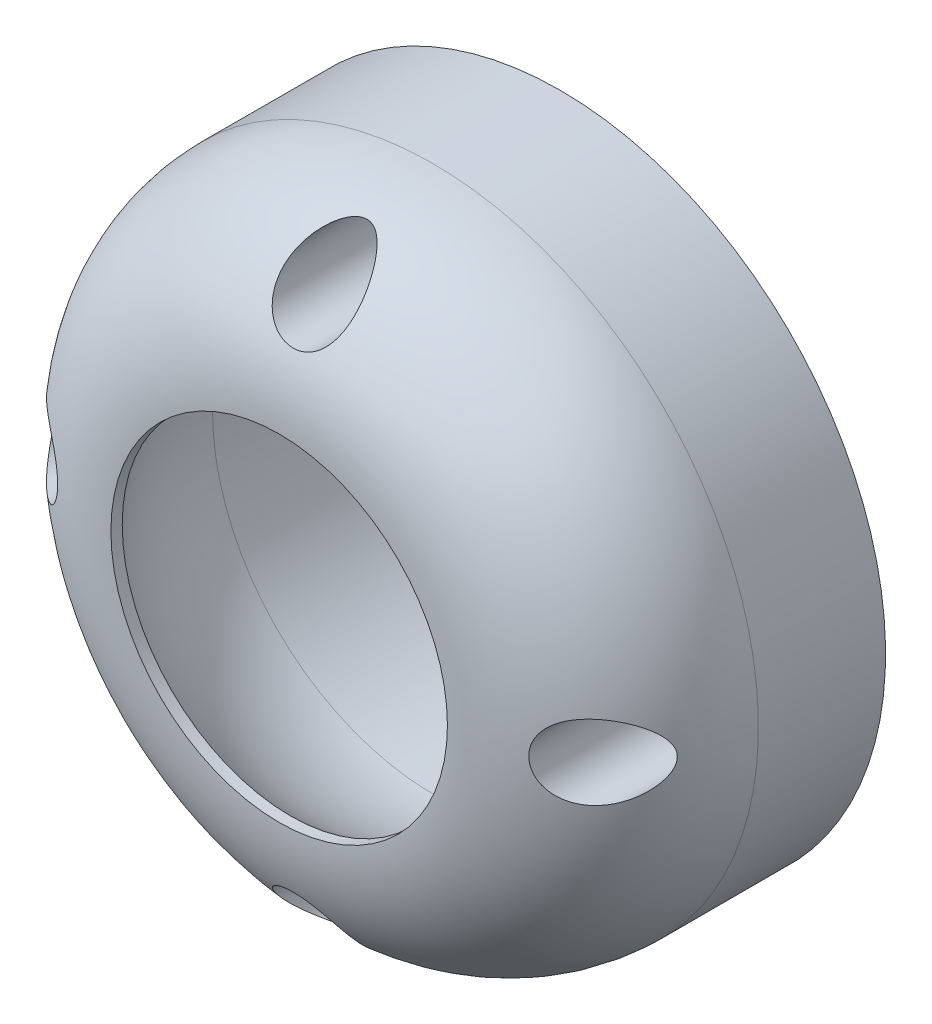
SolidWorks part; units mm, degrees
ref_plane "正面" through (0, 0, 0) normal (0, 0, 1) x (1, 0, 0)
ref_plane "平面" through (0, 0, 0) normal (0, 1, 0) x (1, 0, 0)
ref_plane "右側面" through (0, 0, 0) normal (1, 0, 0) x (0, 0, -1)
sketch "ｽｹｯﾁ1" plane through (0, 0, 0) normal (0, 0, 1) x (1, 0, 0)
  line L0 (-15.25, 0) -> (-14.75, 0)
  line L1 (14.75, 0) -> (15.25, 0)
  line L2 (14.75, 0) -> (-14.75, 0) construction
  arc A0 (14.75, 0) -> (-14.75, 0) centre (0, 0) cw
  arc A1 (-15.25, 0) -> (15.25, 0) centre (0, 0) ccw
  dimension "D2" = 14.75
  dimension "D1" = 15.25
revolve "回転1" add sketch "ｽｹｯﾁ1" angle 180 about L2
sketch "ｽｹｯﾁ2" plane through (0, 0, 0) normal (0, 0, -1) x (-1, 0, 0)
  circle A0 centre (0, 0) radius 11.25
  dimension "D1" = 22.5
extrude "ｶｯﾄ - 押し出し1" cut sketch "ｽｹｯﾁ2" against normal through all
sketch "ｽｹｯﾁ4" plane through (0, 0, 0) normal (1, 0, 0) x (0, 0, -1)
  line L0 (0, 15.25) -> (0, 21.75)
  line L1 (0, 0) -> (0, 15.25) construction
  line L2 (0, 0) -> (-17.7206, 0) construction
  arc A0 (-10.2956, 11.25) -> (0, 21.75) centre (0, 11.4524) cw
  arc A1 (0, 15.25) -> (-10.2956, 11.25) centre (0, 0) ccw
  arc A2 (0, 15.25) -> (-10.2956, 11.25) centre (0, 0) ccw construction
  dimension "D1" = 6.5
revolve "回転2" add sketch "ｽｹｯﾁ4" angle 360 about L2
sketch "ｽｹｯﾁ3" plane through (0, 0, 0) normal (0, 0, -1) x (-1, 0, 0)
  circle A0 centre (0, 0) radius 14.75
  circle A1 centre (0, 0) radius 21.75
  circle A2 centre (0, 0) radius 14.75 construction
  circle A4 centre (0, 0) radius 21.75 construction
  dimension "D1" = 7
  dimension "D2" = 29.5
  dimension "D3" = 43.5
  dimension "D4" = 14.75
extrude "ﾎﾞｽ - 押し出し1" add sketch "ｽｹｯﾁ3" along normal blind 8.5
sketch "ｽｹｯﾁ7" plane through (0, 0, -8.5) normal (0, 0, -1) x (-1, 0, 0)
  line L0 (0, -14.75) -> (0, 0) construction
  line L1 (0, -14.75) -> (0, -18.25) construction
  line L2 (0, -18.25) -> (0, -21.75) construction
  circle A0 centre (0, 0) radius 18.25 construction
  circle A3 centre (0, -18.25) radius 1.1
  circle A4 centre (-18.25, 0) radius 1.1
  circle A5 centre (0, 18.25) radius 1.1
  circle A6 centre (18.25, 0) radius 1.1
  circle A8 centre (0, 0) radius 21.75 construction
  circle A9 centre (0, 0) radius 14.75 construction
  point P23 (0, 0)
  dimension "D2" = 2.2
  dimension "D3" = 36.5
  dimension "D1" = 4
extrude "ｶｯﾄ - 押し出し2" cut sketch "ｽｹｯﾁ7" against normal through all
ref_plane "平面1" through (0, 0, 0) normal (0, 0, 1) x (1, 0, 0)
sketch "ｽｹｯﾁ8" plane through (0, 0, -8.5) normal (0, 0, 1) x (1, 0, 0)
  line L0 (0, 0) -> (0, 14.75) construction
  line L1 (0, 14.75) -> (0, 18.25) construction
  line L2 (0, 18.25) -> (0, 21.75) construction
  circle A0 centre (0, 0) radius 18.25 construction
  circle A2 centre (0, 18.25) radius 2.5
  circle A3 centre (0, 18.25) radius 1.1 construction
  circle A4 centre (18.25, 0) radius 2.5
  circle A5 centre (0, -18.25) radius 2.5
  circle A6 centre (-18.25, 0) radius 2.5
  circle A7 centre (0, 0) radius 21.75 construction
  point P21 (0, 0)
  point P24 (0, 0)
  dimension "D1" = 5
  dimension "D3" = 3.5
  dimension "D2" = 4
extrude "ｶｯﾄ - 押し出し7" cut sketch "ｽｹｯﾁ8" along normal through all from offset 3
